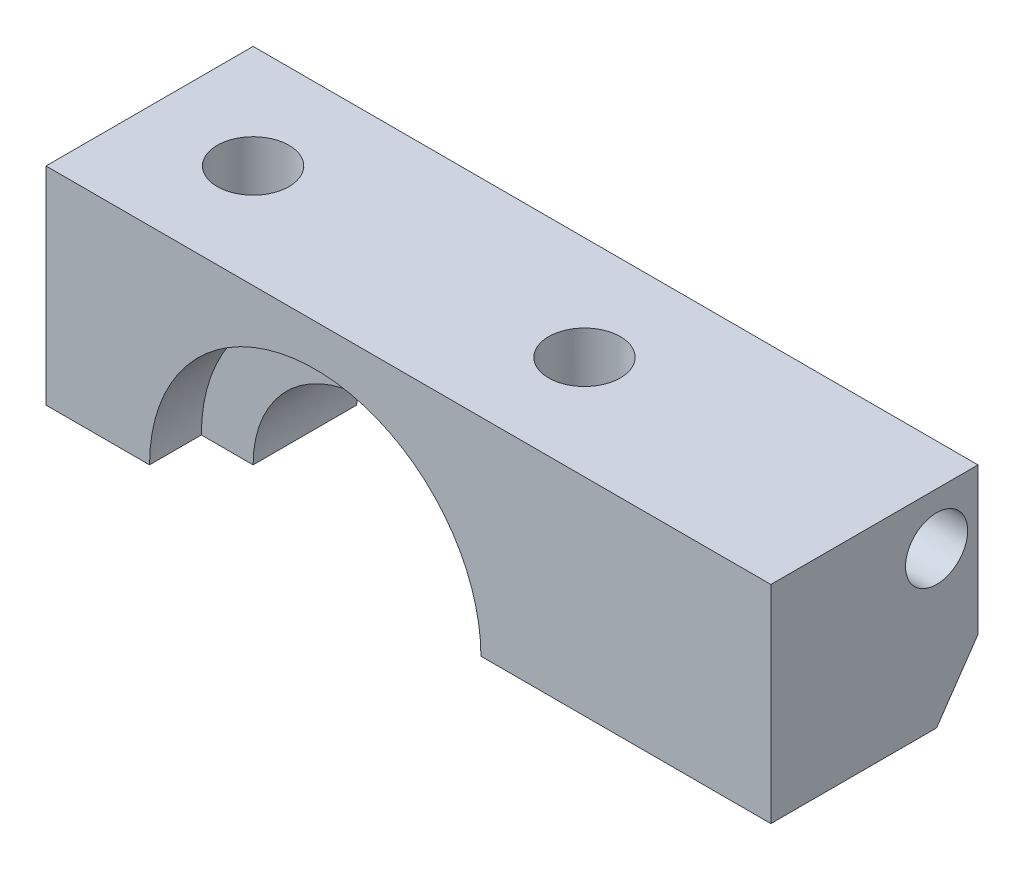
SolidWorks part; units mm, degrees
ref_plane "Plano frontal" through (0, 0, 0) normal (0, 0, 1) x (1, 0, 0)
ref_plane "Plano superior" through (0, 0, 0) normal (0, 1, 0) x (1, 0, 0)
ref_plane "Plano direito" through (0, 0, 0) normal (1, 0, 0) x (0, 0, -1)
sketch "Esboço1" plane through (0, 0, 0) normal (0, 0, 1) x (1, 0, 0)
  line L0 (-5.5, 0) -> (-13, 0)
  line L1 (-13, 0) -> (-13, 10)
  line L2 (-13, 10) -> (13, 10)
  line L3 (13, 10) -> (13, 0)
  line L4 (13, 0) -> (5.5, 0)
  arc A0 (5.5, 0) -> (-5.5, 0) centre (0, 0) ccw
  dimension "D1" = 5.5
  dimension "D2" = 26
  dimension "D3" = 10
extrude "Ressalto-extrusão1" add sketch "Esboço1" along normal mid plane 5
sketch "Esboço3" plane through (0, 0, 0) normal (0, 0, 1) x (1, 0, 0)
  line L0 (-13, 10) -> (-13, 0)
  line L1 (-13, 0) -> (-8, 0)
  line L2 (8, 0) -> (13, 0)
  line L3 (13, 0) -> (13, 10)
  line L4 (13, 10) -> (-13, 10)
  arc A0 (8, 0) -> (-8, 0) centre (0, 0) ccw
  dimension "D1" = 8
extrude "Ressalto-extrusão2" add sketch "Esboço3" along normal mid plane 10
sketch "Esboço2" plane through (0, 0, 0) normal (0, -1, 0) x (1, 0, 0)
  line L0 (0, 0) -> (0, 9.5392) construction
  line L1 (-5.5, 2.5) -> (-5.5, -2.5) construction
  circle A0 centre (-8, 0) radius 1.7309
  circle A1 centre (8, 0) radius 1.7309
  point P7 (-5.5, 0)
  dimension "D1" = 16
extrude "Corte-extrusão1" cut sketch "Esboço2" against normal blind 15
sketch "Esboço5" plane through (13, 0, 0) normal (1, 0, 0) x (0, 0, -1)
  line L0 (-5, 10) -> (-5, 0)
  line L1 (5, 2.9131) -> (3, 0)
  line L2 (5, 0) -> (5, 10) construction
  line L3 (5, 2.9131) -> (5, 10)
  line L4 (5, 10) -> (-5, 10)
  line L5 (-5, 0) -> (5, 0) construction
  line L6 (3, 0) -> (-5, 0)
  circle A0 centre (3, 7.5) radius 1.5
  point P4 (-0.2789, 0)
  point P12 (0, 0)
  point P13 (5, 1.3654)
  point P17 (3, 0)
  point P18 (5, 2.9131)
  dimension "D1" = 3
  dimension "D2" = 2.5
  dimension "D3" = 2
extrude "Ressalto-extrusão4" add sketch "Esboço5" along normal blind 9
